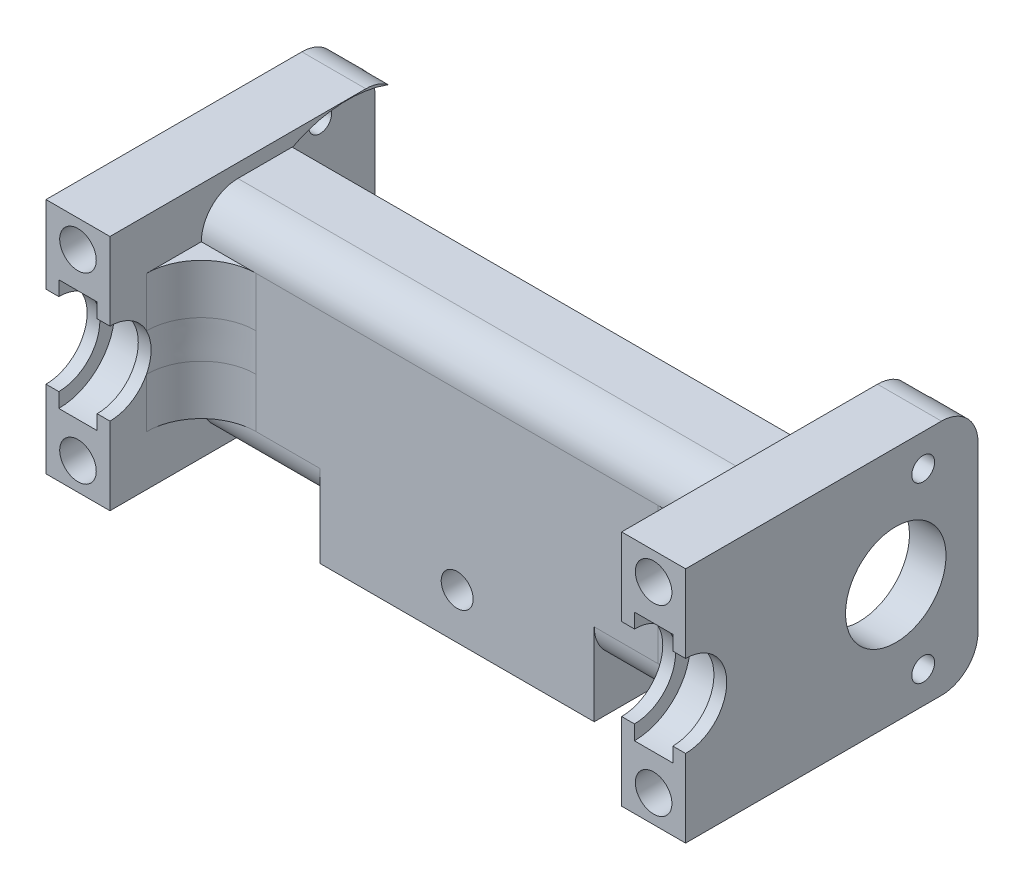
SolidWorks part; units mm, degrees
ref_plane "Front Plane" through (0, 0, 0) normal (0, 0, 1) x (1, 0, 0)
ref_plane "Top Plane" through (0, 0, 0) normal (0, 1, 0) x (1, 0, 0)
ref_plane "Right Plane" through (0, 0, 0) normal (1, 0, 0) x (0, 0, -1)
sketch "Sketch1" plane through (0, 0, 0) normal (0, 0, 1) x (1, 0, 0)
  line L1 (-35, 7.5) -> (35, 7.5)
  line L2 (-35, 7.5) -> (-35, -7.5)
  line L3 (-35, -7.5) -> (35, -7.5)
  line L4 (35, 7.5) -> (35, -7.5)
  line L5 (-35, 7.5) -> (35, -7.5) construction
  line L6 (-35, -7.5) -> (35, 7.5) construction
  point P0 (0, 0)
  dimension "D1" = 15
  dimension "D2" = 70
extrude "Boss-Extrude1" add sketch "Sketch1" along normal blind 3
sketch "Sketch2" plane through (0, 0, 3) normal (0, 0, 1) x (1, 0, 0)
  line L0 (-35, -7.5) -> (35, -7.5) construction
  line L1 (-35, 7.5) -> (-28, 7.5)
  line L2 (-35, 7.5) -> (-35, -7.5)
  line L3 (-35, -7.5) -> (-28, -7.5)
  line L4 (-28, 7.5) -> (-28, -7.5)
  line L6 (35, 7.5) -> (28, 7.5)
  line L7 (35, 7.5) -> (35, -7.5)
  line L8 (35, -7.5) -> (28, -7.5)
  line L9 (28, 7.5) -> (28, -7.5)
  dimension "D1" = 7
  dimension "D2" = 7
extrude "Boss-Extrude2" add sketch "Sketch2" along normal blind 10
sketch "Sketch5" plane through (35, 0, 0) normal (1, 0, 0) x (0, 0, -1)
  line L0 (-13, -7.5) -> (-13, 7.5) construction
  circle A0 centre (-13, 0) radius 4.5
  dimension "D1" = 9
extrude "Cut-Extrude1" cut sketch "Sketch5" against normal through all
ref_plane "Plane1" through (31.5, 0, 0) normal (1, 0, 0) x (0, 0, -1)
sketch "Sketch6" plane through (31.5, 0, 0) normal (1, 0, 0) x (0, 0, -1)
  circle A0 centre (-13, 0) radius 6.1
  dimension "D1" = 12.2
extrude "Cut-Extrude4" cut sketch "Sketch6" against normal blind 2.1 and the other way blind 2.1
sketch "Sketch7" plane through (0, 0, 0) normal (0, 0, 1) x (1, 0, 0)
  line L1 (28, 8.1) -> (28, 13)
  line L2 (28, 13) -> (35, 13)
  line L3 (35, 13) -> (35, 8.1)
  line L4 (35, 7.5) -> (28, 7.5) construction
  line L9 (29.4, 6.1) -> (33.6, 6.1)
  line L10 (29.4, 6.1) -> (33.6, 6.1)
  line L11 (33.6, 6.1) -> (33.6, 4.5)
  line L12 (33.6, 4.5) -> (35, 4.5)
  line L13 (35, 4.5) -> (35, 7.5)
  line L14 (35, 7.5) -> (28, 7.5)
  line L15 (28, 7.5) -> (28, 4.5)
  line L16 (33.6, 6.1) -> (33.6, 4.5)
  line L17 (28, 4.5) -> (29.4, 4.5)
  line L20 (33.6, 4.5) -> (35, 4.5)
  line L21 (35, 4.5) -> (35, 8.1)
  line L23 (28, 8.1) -> (28, 4.5)
  line L26 (28, 4.5) -> (29.4, 4.5)
  line L27 (29.4, 4.5) -> (29.4, 6.1)
  line L28 (29.4, 4.5) -> (29.4, 6.1)
  dimension "D2" = 5.5
  dimension "D1" = 0
extrude "Boss-Extrude3" add sketch "Sketch7" along normal blind 13
sketch "Sketch8" plane through (0, 0, 13) normal (0, 0, 1) x (1, 0, 0)
  line L0 (31.5, 13) -> (31.5, 10) construction
  line L1 (35, 13) -> (28, 13) construction
  circle A0 centre (31.5, 10) radius 2
  dimension "D1" = 4
  dimension "D2" = 3
extrude "Cut-Extrude5" cut sketch "Sketch8" against normal through all both and the other way through all
sketch "Sketch9" plane through (0, 0, 3) normal (0, 0, 1) x (1, 0, 0)
  circle A0 centre (-10, -4) radius 1.75
  dimension "D3" = 3.5
  dimension "D1" = 10
  dimension "D2" = 4
extrude "Cut-Extrude6" cut sketch "Sketch9" against normal through all
mirror "Mirror1" about plane through (0, 0, 0) normal (1, 0, 0) of "Cut-Extrude6", "Cut-Extrude5", "Boss-Extrude3", "Cut-Extrude4" second plane through (0, 0, 0) second plane normal (0, 1, 0)
fillet "Fillet1" radius 6 2 edges at (28, 0, 3) (-28, 0, 3)
sketch "Sketch10" plane through (0, 0, 3) normal (0, 0, -1) x (-1, 0, 0)
  line L1 (-28, -11.5) -> (28, -11.5)
  line L2 (-28, -11.5) -> (-28, 11.5)
  line L3 (-28, 11.5) -> (28, 11.5)
  line L4 (28, -11.5) -> (28, 11.5)
  line L5 (-28, -11.5) -> (28, 11.5) construction
  line L6 (-28, 11.5) -> (28, -11.5) construction
  point P0 (0, 0)
  dimension "D1" = 23
  dimension "D2" = 56
extrude "Boss-Extrude4" add sketch "Sketch10" along normal blind 15
fillet "Fillet2" radius 4 2 edges at (0, 11.5, 3) (0, -11.5, 3)
sketch "Sketch11" plane through (28, 0, 0) normal (1, 0, 0) x (0, 0, -1)
  line L0 (0, 0) -> (13, 0) construction
  circle A0 centre (13, 0) radius 13
  dimension "D1" = 26
extrude "Cut-Extrude7" cut sketch "Sketch11" against normal through all
sketch "Sketch14" plane through (0, 0, 0) normal (0, 0, -1) x (-1, 0, 0)
  line L0 (35, 13) -> (35, -13) construction
  line L1 (35, 13) -> (28, 13)
  line L2 (35, 13) -> (35, -13)
  line L3 (35, -13) -> (28, -13)
  line L4 (28, 13) -> (28, -13)
  line L5 (28, 0) -> (28, -11.373) construction
  line L6 (28, 0) -> (0, 0) construction
  dimension "D1" = 26
extrude "Boss-Extrude6" add sketch "Sketch14" along normal blind 5
sketch "Sketch15" plane through (0, 0, -5) normal (0, 0, -1) x (-1, 0, 0)
  line L0 (31.5, 0) -> (28, 0) construction
  line L1 (28, -13) -> (35, -13)
  line L2 (28, -13) -> (28, 13)
  line L3 (28, 13) -> (35, 13)
  line L4 (35, -13) -> (35, 13)
  line L5 (28, -13) -> (35, 13) construction
  line L6 (28, 13) -> (35, -13) construction
  line L8 (31.5, 0) -> (31.5, -13) construction
  line L9 (28, -13) -> (35, -13) construction
  line L10 (28, 10.247) -> (28, -10.247) construction
  point P0 (31.5, 0)
  dimension "D1" = 26
extrude "Boss-Extrude7" add sketch "Sketch15" along normal blind 14
fillet "Fillet5" radius 4 2 edges at (-31.5, 13, -19) (-31.5, -13, -19)
sketch "Sketch16" plane through (-35, 0, 0) normal (-1, 0, 0) x (0, 0, 1)
  line L0 (0, -8) -> (0, 8) construction
  line L1 (0, 0) -> (-10, 0) construction
  circle A0 centre (-10, 0) radius 5.5
  dimension "11" = 11
  dimension "D1" = 10
extrude "Cut-Extrude9" cut sketch "Sketch16" against normal through all
mirror "Mirror2" about plane through (0, 0, 0) normal (1, 0, 0) of "Boss-Extrude6", "Boss-Extrude7", "Fillet5", "Cut-Extrude9"
sketch "Sketch17" plane through (-35, 0, 0) normal (-1, 0, 0) x (0, 0, 1)
  line L0 (-10, 0) -> (-13, 0) construction
  line L1 (-13, 0) -> (-13, 9.5) construction
  line L2 (-13, 0) -> (-13, -9.5) construction
  circle A0 centre (-13, 9.5) radius 1.25
  circle A1 centre (-13, -9.5) radius 1.25
  dimension "D4" = 2.5
  dimension "D5" = 2.5
  dimension "D1" = 3
  dimension "D2" = 9.5
  dimension "D3" = 9.5
extrude "Cut-Extrude10" cut sketch "Sketch17" against normal through all
sketch "Sketch18" plane through (0, 0, 0) normal (1, 0, 0) x (0, 0, -1)
  line L0 (13, 9.5) -> (13, -9.5) construction
  circle A0 centre (13, 0) radius 12.95
  dimension "D1" = 25.9
extrude "Cut-Extrude14" cut sketch "Sketch18" against normal blind 31 and the other way blind 31
sketch "Sketch19" plane through (0, -11.5, 0) normal (0, -1, 0) x (1, 0, 0)
  line L0 (-22, 3) -> (22, 3) construction
  line L1 (-15, -7) -> (15, -7)
  line L2 (-15, -7) -> (-15, 3)
  line L3 (-15, 3) -> (15, 3)
  line L4 (15, -7) -> (15, 3)
  line L5 (-15, -7) -> (15, 3) construction
  line L6 (-15, 3) -> (15, -7) construction
  line L8 (0, 0) -> (0, -2) construction
  point P0 (0, -2)
  point P7 (10.242, -4.1508)
  dimension "D1" = 30
  dimension "D2" = 10
extrude "Boss-Extrude8" add sketch "Sketch19" along normal blind 5 and the other way up to next
sketch "Sketch20" plane through (0, -16.5, 0) normal (0, -1, 0) x (1, 0, 0)
  line L0 (-8.5, -3) -> (8.5, -3) construction
  line L1 (0, -3) -> (0, 0) construction
  line L2 (15, 3) -> (-15, 3) construction
  circle A0 centre (-8.5, -3) radius 2
  circle A1 centre (8.5, -3) radius 2
  dimension "D2" = 4
  dimension "D3" = 4
  dimension "D1" = 17
  dimension "D4" = 6
extrude "Cut-Extrude15" cut sketch "Sketch20" against normal blind 10
sketch "Sketch21" plane through (0, 0, 3) normal (0, 0, 1) x (1, 0, 0)
  line L0 (0, -11.5) -> (0, -16.5) construction
  line L1 (15, -16.5) -> (-15, -16.5) construction
  circle A0 centre (0, -11.5) radius 1.75
  dimension "D2" = 3.5
  dimension "D1" = 5
extrude "Cut-Extrude16" cut sketch "Sketch21" against normal through all
